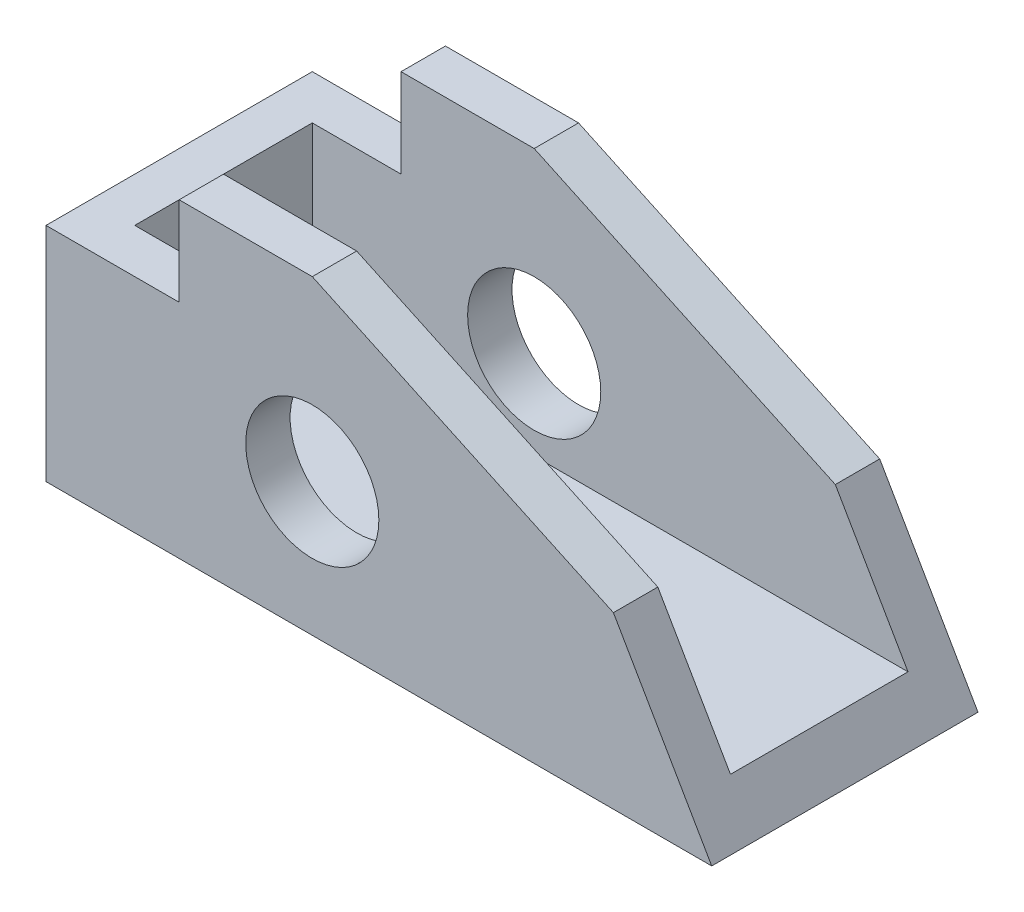
SolidWorks part; units mm, degrees
ref_plane "Front Plane" through (0, 0, 0) normal (0, 0, 1) x (1, 0, 0)
ref_plane "Top Plane" through (0, 0, 0) normal (0, 1, 0) x (1, 0, 0)
ref_plane "Right Plane" through (0, 0, 0) normal (1, 0, 0) x (0, 0, -1)
sketch "Sketch1" plane through (0, 0, 0) normal (0, 1, 0) x (1, 0, 0)
  line L1 (0, 0) -> (95.25, 0)
  line L2 (0, 0) -> (0, 38.1)
  line L3 (0, 38.1) -> (95.25, 38.1)
  line L4 (95.25, 0) -> (95.25, 38.1)
  dimension "D1" = 95.25
  dimension "D2" = 38.1
extrude "Boss-Extrude1" add sketch "Sketch1" along normal blind 44.45
hole_wizard "3/4 (0.75) Diameter Hole1" positions "Sketch2" profile "Sketch3" hole size "3/4" standard "ANSI Inch" end condition through all
sketch "Sketch2" plane through (0, 0, 0) normal (0, 0, 1) x (1, 0, 0)
  line L0 (0, 44.45) -> (0, 0) construction
  line L1 (0, 0) -> (95.25, 0) construction
  point P0 (38.1, 19.05)
  dimension "D1" = 38.1
  dimension "D2" = 19.05
sketch "Sketch3" plane through (38.1, 19.05, 0) normal (1, 0, 0) x (0, -1, 0)
  line L0 (0, 0) -> (0, 38.1)
  line L1 (0, 38.1) -> (9.525, 38.1)
  line L2 (9.525, 38.1) -> (9.525, 0)
  line L5 (9.525, 0) -> (0, 0)
  line L11 (0, -6.35) -> (0, 107.95) construction
  dimension "Thru Hole Dia." = 19.05
  dimension "Thru Hole Depth" = 38.1
sketch "Sketch4" plane through (0, 44.45, 0) normal (0, 1, 0) x (1, 0, 0)
  line L0 (0, 0) -> (95.25, 0) construction
  line L1 (0, 38.1) -> (19.05, 38.1)
  line L2 (0, 38.1) -> (0, 0)
  line L3 (0, 0) -> (19.05, 0)
  line L4 (19.05, 38.1) -> (19.05, 0)
  dimension "D1" = 19.05
extrude "Cut-Extrude1" cut sketch "Sketch4" against normal blind 12.7
sketch "Sketch5" plane through (0, 0, 0) normal (0, 0, 1) x (1, 0, 0)
  line L0 (38.1, 44.45) -> (95.25, 17.8005)
  line L3 (19.05, 44.45) -> (95.25, 44.45) construction
  line L4 (95.25, 44.45) -> (95.25, 0) construction
  line L6 (38.1, 44.45) -> (95.25, 44.45)
  line L7 (95.25, 44.45) -> (95.25, 17.8005)
  dimension "D1" = 38.1
  dimension "D2" = 25
extrude "Cut-Extrude2" cut sketch "Sketch5" against normal up to next
sketch "Sketch6" plane through (0, 0, 0) normal (0, 0, 1) x (1, 0, 0)
  line L0 (95.25, 0) -> (81.1867, 24.3583)
  line L1 (38.1, 44.45) -> (95.25, 17.8005) construction
  line L2 (0, 0) -> (95.25, 0) construction
  line L4 (81.1867, 24.3583) -> (95.25, 24.3583)
  line L7 (95.25, 24.3583) -> (95.25, 0)
  dimension "D1" = 60
extrude "Cut-Extrude3" cut sketch "Sketch6" against normal up to next
sketch "Sketch7" plane through (0, 44.45, 0) normal (0, 1, 0) x (1, 0, 0)
  line L0 (95.25, 0) -> (95.25, 38.1) construction
  line L1 (6.35, 31.75) -> (95.25, 31.75)
  line L2 (6.35, 31.75) -> (6.35, 6.35)
  line L3 (6.35, 6.35) -> (95.25, 6.35)
  line L4 (95.25, 31.75) -> (95.25, 6.35)
  line L5 (0, 38.1) -> (0, 0) construction
  line L6 (19.05, 0) -> (38.1, 0) construction
  line L7 (38.1, 38.1) -> (19.05, 38.1) construction
  dimension "D1" = 6.35
  dimension "D2" = 6.35
  dimension "D3" = 6.35
extrude "Cut-Extrude4" cut sketch "Sketch7" against normal blind 38.1
